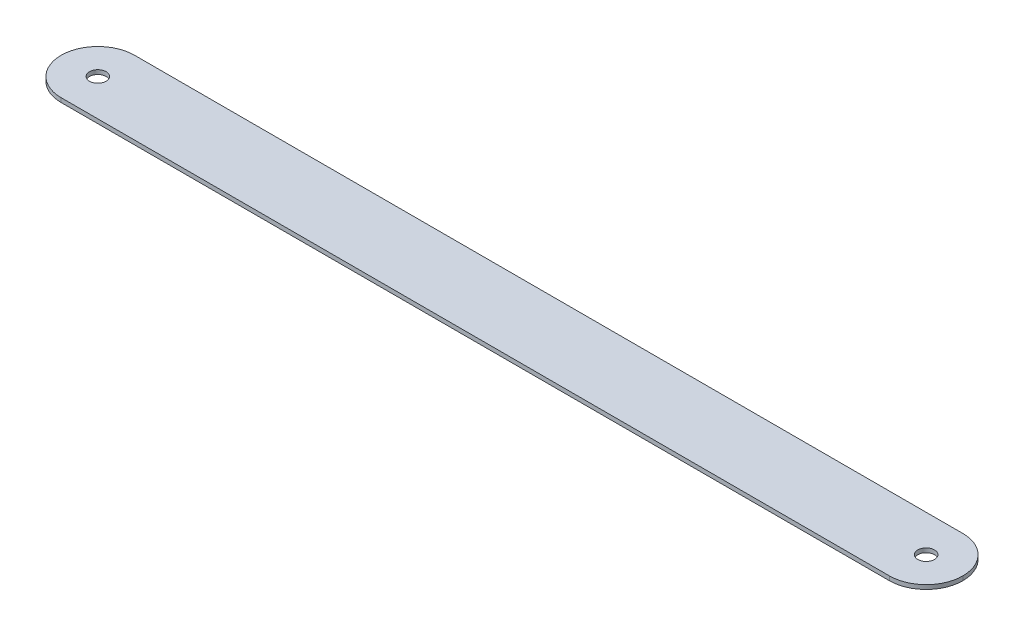
SolidWorks part; units mm, degrees
ref_plane "Front Plane" through (0, 0, 0) normal (0, 0, 1) x (1, 0, 0)
ref_plane "Top Plane" through (0, 0, 0) normal (0, 1, 0) x (1, 0, 0)
ref_plane "Right Plane" through (0, 0, 0) normal (1, 0, 0) x (0, 0, -1)
sketch "Sketch2" plane through (0, 0, 0) normal (0, 1, 0) x (1, 0, 0)
  line L1 (92.075, -7.5) -> (-92.075, -7.5)
  line L2 (92.075, -7.5) -> (92.075, 7.5)
  line L3 (92.075, 7.5) -> (-92.075, 7.5)
  line L4 (-92.075, -7.5) -> (-92.075, 7.5)
  line L5 (92.075, -7.5) -> (-92.075, 7.5) construction
  line L6 (92.075, 7.5) -> (-92.075, -7.5) construction
  point P0 (0, 0)
  dimension "D1" = 184.15
  dimension "D2" = 15
base flange "Base-Flange1" sketch "Sketch2" thickness 0.86 reverse thickness direction no parameters "D1"=0.7366
hole_wizard "M3 Clearance Hole1" positions "Sketch8" profile "Sketch7" hole size "M3" standard "ANSI Metric"
sketch "Sketch8" plane through (0, 0, 0) normal (0, 1, 0) x (1, 0, 0)
  line L0 (-92.075, 7.5) -> (-92.075, -7.5) construction
  line L1 (92.075, -7.5) -> (92.075, 7.5) construction
  point P0 (-84.575, 0)
  point P2 (84.575, 0)
  point P7 (92.075, 0)
  dimension "D1" = 7.5
  dimension "D2" = 7.5
sketch "Sketch7" plane through (-84.575, 0, 0) normal (1, 0, 0) x (0, 0, 1)
  line L0 (0, 0) -> (0, 2.3115)
  line L1 (0, 2.3115) -> (1.7, 1.29)
  line L2 (1.7, 1.29) -> (1.7, 0)
  line L5 (1.7, 0) -> (0, 0)
  line L10 (0, 2.3115) -> (-1.7, 1.29) construction
  line L11 (0, -6.35) -> (0, 107.95) construction
  dimension "Hole Dia." = 3.4
  dimension "Hole Depth" = 1.29
  dimension "Drill Angle" = 118
fillet "Fillet1" radius 7.5 4 edges at (92.075, -0.43, 7.5) (92.075, -0.43, -7.5) (-92.075, -0.43, 7.5) (-92.075, -0.43, -7.5)
sketch "Bend-Lines1" [suppressed] plane through (0, 0, 0) normal (0, 1, 0) x (1, 0, 0)
sketch "Bounding-Box1" [suppressed] plane through (0, 0, 0) normal (0, 1, 0) x (1, 0, 0)
sheet metal parameters "Sheet-Metal(1)" thickness 0.86 parameters "D1"=0.7366
flat pattern "Flat-Pattern(1)" [suppressed]
sketch "Bend-Lines2" plane through (0, 0, 0) normal (0, 1, 0) x (1, 0, 0)
sketch "Bounding-Box2" [suppressed] plane through (0, 0, 0) normal (0, 1, 0) x (1, 0, 0)
sheet metal parameters "Sheet-Metal(2)" thickness 0.86 parameters "D1"=0.7366
flat pattern "Flat-Pattern(1)"
sketch "Bend-Lines2" plane through (0, 0, 0) normal (0, 1, 0) x (1, 0, 0)
sketch3d "Bounding-Box2" [suppressed]
  line L0 (92.075, -7.5, 0) -> (-92.075, -7.5, 0) construction
  line L1 (92.075, 7.5, 0) -> (-92.075, 7.5, 0) construction
  line L2 (92.075, -7.5, 0) -> (92.075, 7.5, 0) construction
  line L3 (-92.075, -7.5, 0) -> (-92.075, 7.5, 0) construction
